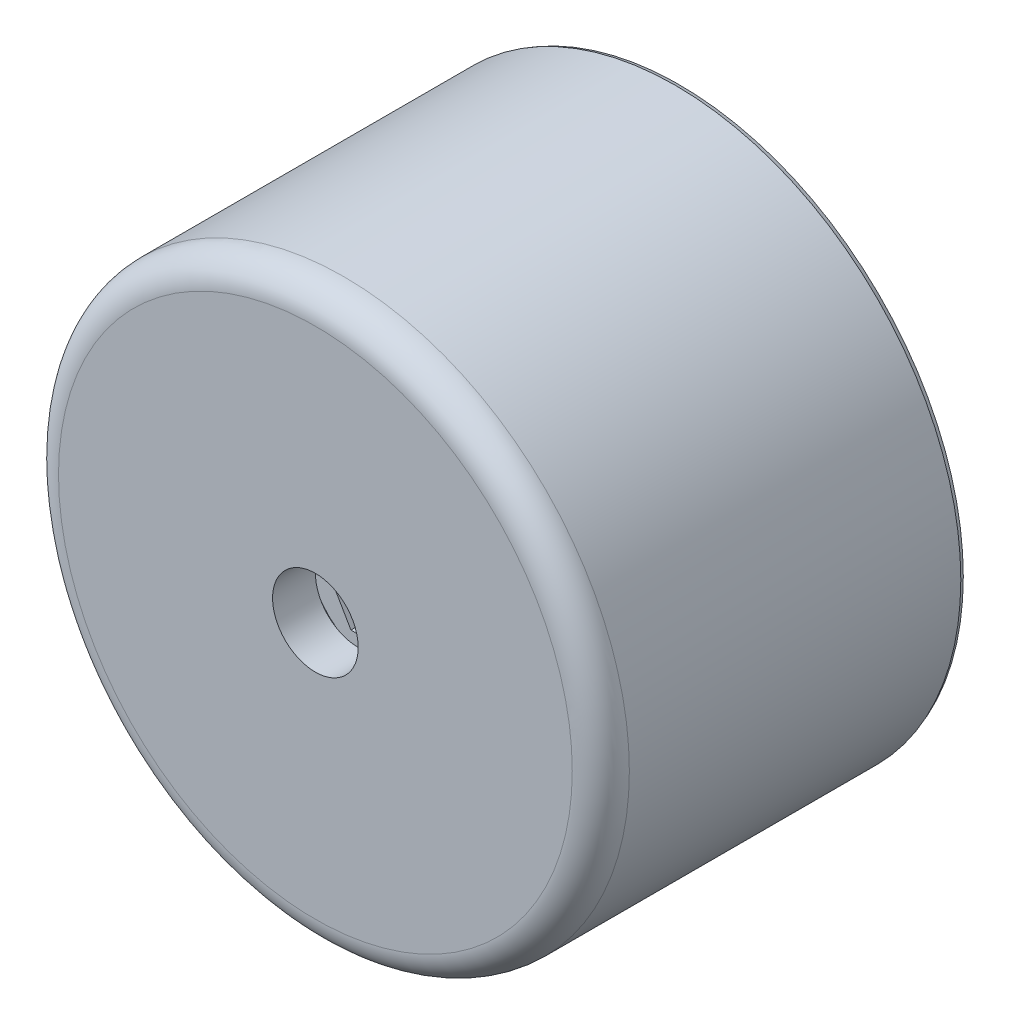
SolidWorks part; units mm, degrees
ref_plane "Front Plane" through (0, 0, 0) normal (0, 0, 1) x (1, 0, 0)
ref_plane "Top Plane" through (0, 0, 0) normal (0, 1, 0) x (1, 0, 0)
ref_plane "Right Plane" through (0, 0, 0) normal (1, 0, 0) x (0, 0, -1)
sketch "Sketch1" plane through (0, 0, 0) normal (0, 0, 1) x (1, 0, 0)
  circle A0 centre (-11.8226, 14.5298) radius 20
  circle A1 centre (-11.8226, 14.5298) radius 1
  dimension "D1" = 40
  dimension "D2" = 2
extrude "Boss-Extrude1" add sketch "Sketch1" along normal blind 22.5
hole_wizard "Tap Drill for M5x0.8 Tap1" positions "Sketch2" profile "Sketch3" hole size "M5x0.8" standard "ANSI Metric"
sketch "Sketch2" plane through (0, 0, 22.5) normal (0, 0, 1) x (1, 0, 0)
  point P0 (-11.8226, 14.5298)
sketch "Sketch3" plane through (-11.8226, 14.5298, 22.5) normal (1, 0, 0) x (0, -1, 0)
  line L0 (0, 0) -> (0, 6.2618)
  line L1 (0, 6.2618) -> (2.1, 5)
  line L2 (2.1, 5) -> (2.1, 0)
  line L5 (2.1, 0) -> (0, 0)
  line L10 (0, 6.2618) -> (-2.1, 5) construction
  line L11 (0, -6.35) -> (0, 107.95) construction
  dimension "Hole Dia." = 4.2
  dimension "Hole Depth" = 5
  dimension "Drill Angle" = 118
sketch "Sketch4" plane through (0, 0, 22.5) normal (0, 0, 1) x (1, 0, 0)
  line L1 (6.1774, 17.8338) -> (3.3834, 17.8338)
  line L2 (6.1774, 17.8338) -> (6.1774, 11.2298)
  line L3 (6.1774, 11.2298) -> (3.3834, 11.2298)
  line L4 (3.3834, 17.8338) -> (3.3834, 11.2298)
  circle A0 centre (-11.8226, 14.5298) radius 1 construction
  circle A1 centre (-11.8226, 14.5298) radius 20 construction
  dimension "D1" = 6.604
  dimension "D2" = 2.794
  dimension "D3" = 3.3
  dimension "D4" = 18
extrude "Cut-Extrude1" cut sketch "Sketch4" against normal blind 20.5
ref_axis "Axis1" through (-11.8226, 14.5298, 22.5) along (0, 0, -1)
pattern_circular "CirPattern1" count 8 over 360 about axis through (-11.8226, 14.5298, 22.5) along (0, 0, -1) of "Cut-Extrude1"
sketch "Sketch6" plane through (0, 0, 22.5) normal (0, 0, 1) x (1, 0, 0)
  line L0 (-9.5126, 18.5298) -> (-7.2008, 14.5298)
  line L1 (-14.1326, 18.5298) -> (-9.5126, 18.5298)
  line L2 (-14.1326, 18.5298) -> (-14.1326, 10.5298)
  line L3 (-14.1326, 10.5298) -> (-9.5126, 10.5298)
  line L4 (-9.5126, 18.5298) -> (-9.5126, 10.5298)
  line L5 (-7.2008, 14.5298) -> (-9.5126, 10.5298)
  line L6 (-14.1326, 10.5298) -> (-16.4444, 14.5298)
  line L7 (-16.4444, 14.5298) -> (-14.1326, 18.5298)
  point P4 (-11.8226, 10.5298)
  circle M30 centre (-11.8226, 14.5298) radius 2.1
  dimension "D1" = 8
  dimension "D2" = 4
  dimension "D3" = 4.62
  dimension "D4" = 2.31
  dimension "D5" = 4.62
  dimension "D6" = 4.62
  dimension "D7" = 4.62
  dimension "D8" = 4.62
extrude "Cut-Extrude3" cut sketch "Sketch6" against normal blind 6 contours L7 L6 L2 | L5 L0 L4 | L4 L1 L2 L3 M30 | M30 region at (-9.6049, 14.5298, 22.5) region at (-8.742, 14.5298, 22.5) region at (-14.9032, 14.5298, 22.5) region at (-11.8226, 14.5298, 22.5)
sketch "Sketch7" plane through (0, 0, 22.5) normal (0, 0, 1) x (1, 0, 0)
  circle A0 centre (-11.8226, 14.5298) radius 5.5
  dimension "D1" = 11
extrude "Cut-Extrude4" cut sketch "Sketch7" against normal blind 1.8
sketch "Sketch9" plane through (0, 0, 16.5) normal (0, 0, 1) x (1, 0, 0)
  circle A0 centre (-11.8226, 14.5298) radius 3.014
  dimension "D1" = 6.028
extrude "Cut-Extrude5" cut sketch "Sketch9" against normal blind 2
chamfer "Chamfer1" distance 2 angle 45 1 edges at (-8.8085, 14.5298, 14.5)
sketch "Sketch8" plane through (0, 0, 22.5) normal (0, 0, 1) x (1, 0, 0)
  circle A0 centre (-11.8226, 14.5298) radius 3
  circle A1 centre (-11.8226, 14.5298) radius 20
  dimension "D1" = 6
extrude "Boss-Extrude2" add sketch "Sketch8" along normal blind 3
sketch "Sketch5" plane through (0, 0, 0) normal (0, 0, -1) x (-1, 0, 0)
  circle A0 centre (11.8226, 14.5298) radius 5
  circle A1 centre (11.8226, 14.5298) radius 6
  dimension "D1" = 10
  dimension "D2" = 12
extrude "Cut-Extrude2" cut sketch "Sketch5" against normal blind 0.9091
fillet "Fillet3" radius 0.5 2 edges at (-16.8226, 14.5298, 0.9091) (-17.8226, 14.5298, 0.9091)
fillet "Fillet4" radius 2 1 edges at (8.1774, 14.5298, 25.5)
chamfer "Chamfer2" distance 0.1 angle 70 1 edges at (8.1774, 14.5298, 0) first distance on face at (-17.8226, 14.5298, 0)
equation "\"D2@Sketch4\"=25.4*.11"
equation "\"D3@Sketch4\"=6.6/2"
equation "\"oringdiameter\"= 11"
equation "\"oringthickness\"= 2"
equation "\"D2@Sketch5\"=\"oringdiameter\" + \"oringthickness\"/2"
equation "\"D1@Sketch5\"=\"oringdiameter\" - \"oringthickness\"/2"
equation "\"D1@Cut-Extrude2\"=\"oringthickness\"/2.2"
equation "\"D1@Sketch4\"=25.4*.26"
equation "\"D3@Sketch6\"=4.62"
